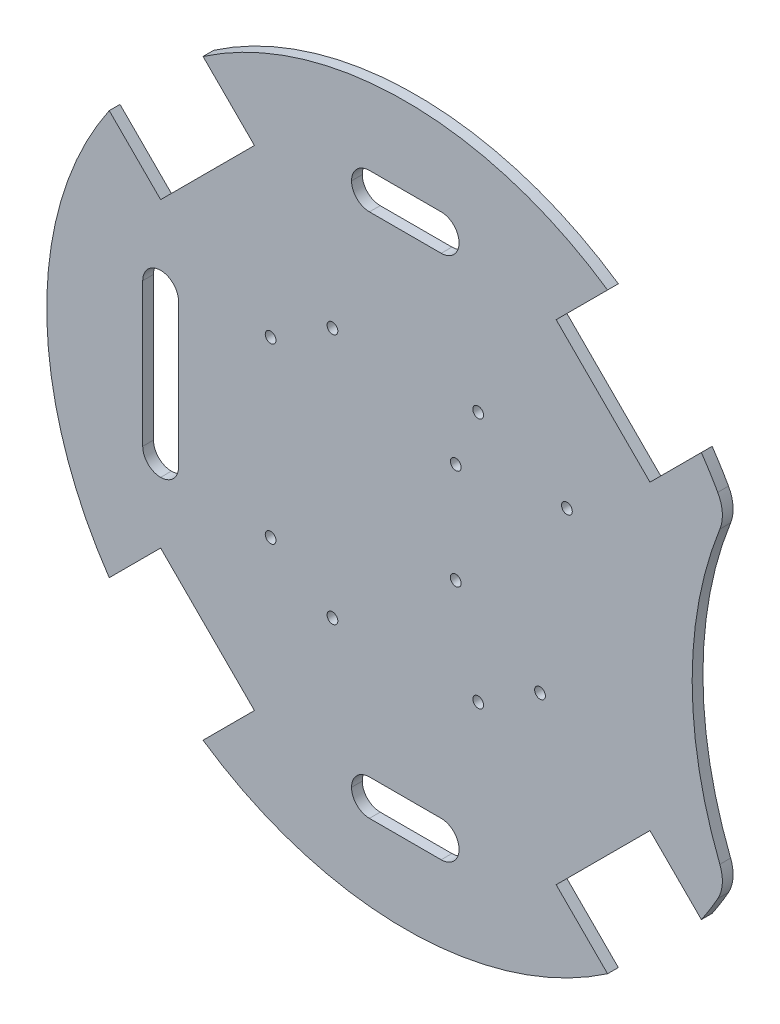
SolidWorks part; units mm, degrees
ref_plane "Alzado" through (0, 0, 0) normal (0, 0, 1) x (1, 0, 0)
ref_plane "Planta" through (0, 0, 0) normal (0, 1, 0) x (1, 0, 0)
ref_plane "Vista lateral" through (0, 0, 0) normal (1, 0, 0) x (0, 0, -1)
sketch "Croquis1" plane through (0, 0, 0) normal (0, 0, 1) x (1, 0, 0)
  circle A0 centre (0, 0) radius 100
  dimension "D1" = 200
extrude "Saliente-Extruir1" add sketch "Croquis1" along normal blind 3
sketch "Croquis3" plane through (0, 0, 3) normal (0, 0, 1) x (1, 0, 0)
  line L0 (0, 0) -> (190, 0) construction
  circle A0 centre (190, 0) radius 110
  dimension "D1" = 220
  dimension "D2" = 190
extrude "Cortar-Extruir1" cut sketch "Croquis3" against normal blind 3
fillet "Redondeo1" radius 10 2 edges at (89.4737, -44.6594, 1.5) (89.4737, 44.6594, 1.5)
sketch "Croquis4" plane through (0, 0, 3) normal (0, 0, 1) x (1, 0, 0)
  line L0 (0, 0) -> (-70.7107, -70.7107) construction
  line L1 (-57.6292, -83.7922) -> (-83.7922, -57.6292)
  line L2 (-57.6292, 83.7922) -> (-42.0729, 68.2358)
  line L3 (-83.7922, -57.6292) -> (-68.2358, -42.0729)
  line L4 (-68.2358, -42.0729) -> (-42.0729, -68.2358)
  line L5 (-42.0729, -68.2358) -> (-57.6292, -83.7922)
  line L6 (-42.0729, 68.2358) -> (-68.2358, 42.0729)
  line L7 (-68.2358, 42.0729) -> (-83.7922, 57.6292)
  line L8 (-83.7922, 57.6292) -> (-57.6292, 83.7922)
  line L9 (83.7922, 57.6292) -> (68.2358, 42.0729)
  line L10 (68.2358, 42.0729) -> (42.0729, 68.2358)
  line L11 (42.0729, 68.2358) -> (57.6292, 83.7922)
  line L12 (57.6292, 83.7922) -> (83.7922, 57.6292)
  line L13 (57.6292, -83.7922) -> (42.0729, -68.2358)
  line L14 (42.0729, -68.2358) -> (68.2358, -42.0729)
  line L15 (68.2358, -42.0729) -> (83.7922, -57.6292)
  line L16 (83.7922, -57.6292) -> (57.6292, -83.7922)
  arc A0 (87.1345, 49.0671) -> (87.1345, -49.0671) centre (0, 0) ccw construction
  point P25 (0, 0)
  dimension "D3" = 18.5
  dimension "D4" = 78
  dimension "D1" = 22
  dimension "D2" = 37
  dimension "D5" = 4
extrude "Cortar-Extruir2" cut sketch "Croquis4" against normal through all
sketch "Croquis6" plane through (0, 0, 3) normal (0, 0, 1) x (1, 0, 0)
  line L0 (-68.2358, -42.0729) -> (-68.1778, 42.4239) construction
  line L3 (-42.0729, -68.2358) -> (42.0729, -68.2358) construction
  line L4 (-63.2358, -25) -> (-63.2358, 25)
  line L5 (-63.2358, 0) -> (0, 0) construction
  line L6 (-63.2358, 25) -> (-73.2358, 25)
  line L7 (-73.2358, 25) -> (-73.2358, -25)
  line L8 (-73.2358, -25) -> (-63.2358, -25)
  line L12 (-15, 78.24) -> (15, 78.24)
  line L13 (-15, 68.24) -> (-15, 78.24)
  line L14 (-15, 68.24) -> (15, 68.24)
  line L15 (15, 78.24) -> (15, 68.24)
  line L19 (-15, -68.24) -> (-15, -78.24)
  line L20 (-15, -78.24) -> (15, -78.24)
  line L21 (-15, -68.24) -> (15, -68.24)
  line L22 (15, -78.24) -> (15, -68.24)
  line L23 (0, 0) -> (0, -68.24) construction
  arc A1 (-82.5716, 56.4086) -> (-82.5716, -56.4086) centre (0, 0) ccw construction
  arc A2 (-56.4086, -82.5716) -> (56.4086, -82.5716) centre (0, 0) ccw construction
  point P44 (0, 0)
  dimension "D1" = 63.2358
  dimension "D2" = 10
  dimension "D3" = 73.2358
  dimension "D4" = 50
  dimension "D5" = 25
  dimension "D6" = 68.24
  dimension "D7" = 10
  dimension "D8" = 30
  dimension "D9" = 15
  dimension "D10" = 78.24
extrude "Cortar-Extruir4" cut sketch "Croquis6" against normal blind 10
fillet "Redondeo3" radius 5 12 edges at (15, -78.24, 1.5) (-15, -78.24, 1.5) (15, -68.24, 1.5) (-15, -68.24, 1.5) (-73.2358, -25, 1.5) (-63.2358, -25, 1.5) (-73.2358, 25, 1.5) (-63.2358, 25, 1.5) (-15, 68.24, 1.5) (15, 68.24, 1.5) (-15, 78.24, 1.5) (15, 78.24, 1.5)
sketch "Croquis7" plane through (0, 0, 0) normal (0, 0, -1) x (-1, 0, 0)
  line L0 (0, 24.17) -> (0, -24.17) construction
  line L2 (37.565, -24.17) -> (-37.565, -24.17) construction
  line L4 (37.565, 24.17) -> (-45.065, 24.17) construction
  line L5 (37.565, 24.17) -> (37.565, -24.17) construction
  line L6 (-45.065, 24.17) -> (-14.0656, 19.2975) construction
  line L7 (-14.0656, 19.2975) -> (37.565, 24.17) construction
  line L8 (37.565, -24.17) -> (-14.0612, -8.7146) construction
  line L9 (-14.0612, -8.7146) -> (-37.565, -24.17) construction
  circle A0 centre (37.565, -24.17) radius 1.5
  circle A1 centre (-37.565, -24.17) radius 1.5
  circle A2 centre (-45.065, 24.17) radius 1.5
  circle A3 centre (37.565, 24.17) radius 1.5
  circle A4 centre (-14.0656, 19.2975) radius 1.5
  circle A5 centre (-14.0612, -8.7146) radius 1.5
  arc A6 (82.5716, -56.4086) -> (82.5716, 56.4086) centre (0, 0) ccw construction
  dimension "D1" = 3
  dimension "D2" = 3
  dimension "D3" = 3
  dimension "D4" = 3
  dimension "D5" = 3
  dimension "D12" = 3
  dimension "D6" = 31.38
  dimension "D7" = 82.63
  dimension "D8" = 51.86
  dimension "D9" = 75.13
  dimension "D10" = 53.89
  dimension "D11" = 28.13
  dimension "D13" = 48.34
  dimension "D14" = 37.565
extrude "Cortar-Extruir5" cut sketch "Croquis7" against normal through all
sketch "Croquis8" plane through (0, 0, 0) normal (0, 0, -1) x (-1, 0, 0)
  line L0 (0, 0) -> (0, 35) construction
  line L1 (20.32, 35) -> (-20.32, 35) construction
  line L2 (0, 0) -> (63.2358, 0) construction
  line L3 (63.2358, -20) -> (63.2358, 20) construction
  circle A0 centre (-20.32, 35) radius 1.5
  circle A1 centre (20.32, 35) radius 1.5
  circle A2 centre (20.32, -35) radius 1.5
  circle A3 centre (-20.32, -35) radius 1.5
  dimension "D1" = 3
  dimension "D2" = 3
  dimension "D3" = 40.64
  dimension "D4" = 20.32
  dimension "D5" = 35
extrude "Cortar-Extruir6" cut sketch "Croquis8" against normal through all
